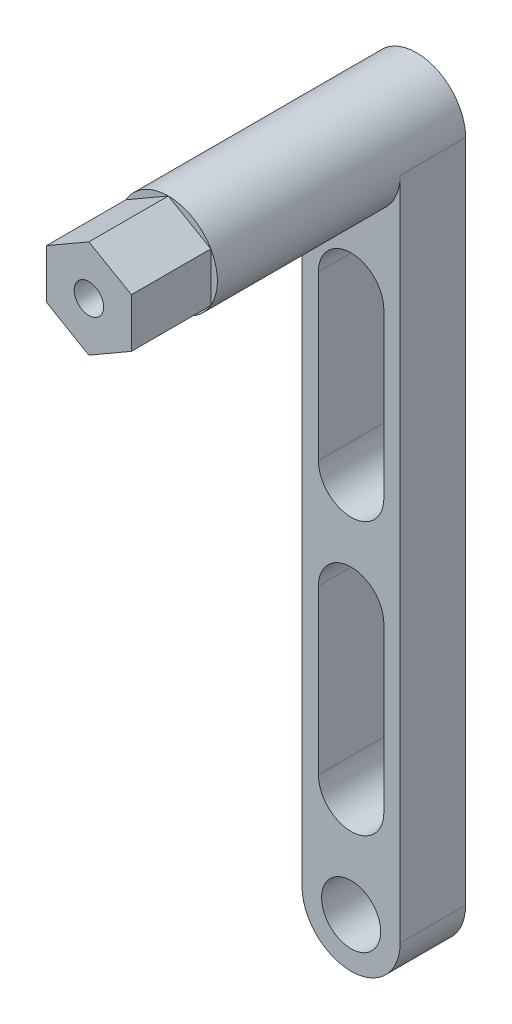
SolidWorks part; units mm, degrees
material "PEI"
ref_plane "Front Plane" through (0, 0, 0) normal (0, 0, 1) x (1, 0, 0)
ref_plane "Top Plane" through (0, 0, 0) normal (0, 1, 0) x (1, 0, 0)
ref_plane "Right Plane" through (0, 0, 0) normal (1, 0, 0) x (0, 0, -1)
sketch "Sketch1" plane through (0, 0, 0) normal (0, 0, 1) x (1, 0, 0)
  line L0 (0, -50.8) -> (0, 50.8) construction
  line L1 (-7.5, -50.8) -> (-7.5, 50.8)
  line L2 (7.5, -50.8) -> (7.5, 50.8)
  line L3 (0, -34.785) -> (0, -9.785) construction
  line L4 (-5, -34.785) -> (-5, -9.785)
  line L5 (5, -34.785) -> (5, -9.785)
  line L6 (0, 31.8) -> (0, 6.8) construction
  line L7 (5, 31.8) -> (5, 6.8)
  line L8 (-5, 31.8) -> (-5, 6.8)
  line L9 (-5, 19.3) -> (5, 19.3) construction
  line L10 (-5, -22.285) -> (5, -22.285) construction
  line L12 (0, 58.3) -> (0, 36.8) construction
  arc A0 (-7.5, -50.8) -> (7.5, -50.8) centre (0, -50.8) ccw
  arc A1 (7.5, 50.8) -> (-7.5, 50.8) centre (0, 50.8) ccw
  circle A2 centre (0, -50.8) radius 4.515
  arc A4 (-5, -34.785) -> (5, -34.785) centre (0, -34.785) ccw
  arc A5 (5, -9.785) -> (-5, -9.785) centre (0, -9.785) ccw
  arc A6 (5, 31.8) -> (-5, 31.8) centre (0, 31.8) ccw
  arc A7 (-5, 6.8) -> (5, 6.8) centre (0, 6.8) ccw
  circle A8 centre (0, 50.8) radius 7.5
  point P2 (0, 0)
  point P14 (0, -22.285)
  point P19 (0, 19.3)
  point P30 (0, -4.785)
  point P32 (0, -46.285)
  point P33 (0, -39.785)
  point P35 (0, 1.8)
  point P37 (0, 43.3)
  dimension "D3" = 9.03
  dimension "D1" = 101.6
  dimension "D2" = 15
  dimension "D4" = 10
  dimension "D5" = 6.5
  dimension "20" = 25
  dimension "D6" = 6.5
extrude "Boss-Extrude1" add sketch "Sketch1" along normal blind 10 contours A8 L1 A0 L2 A7 L8 A6 L7 A5 L5 A4 L4 A2 region at (-6.3987, 0, 0)
extrude "Boss-Extrude2" add sketch "Sketch1<4>" along normal blind 37.94 contours A1 A8 region at (0, 50.8, 0)
sketch "Sketch1<4>" plane through (0, 0, 0) normal (0, 0, 1) x (1, 0, 0) same geometry as "Sketch1"
sketch "Sketch2" plane through (0, 0, 37.94) normal (0, 0, 1) x (1, 0, 0)
  point P0 (0, 50.8)
sketch "Sketch3" plane through (0, 0, 37.94) normal (0, 0, 1) x (1, 0, 0)
  line L1 (0, 43.3) -> (6.4952, 47.05)
  line L2 (6.4952, 47.05) -> (6.4952, 54.55)
  line L3 (6.4952, 54.55) -> (0, 58.3)
  line L4 (0, 58.3) -> (-6.4952, 54.55)
  line L5 (-6.4952, 54.55) -> (-6.4952, 47.05)
  line L6 (-6.4952, 47.05) -> (0, 43.3)
  circle A0 centre (0, 50.8) radius 6.4952 construction
extrude "Boss-Extrude3" add sketch "Sketch3" along normal blind 12.14
sketch "Sketch4" plane through (0, 0, 50.08) normal (0, 0, 1) x (1, 0, 0)
  circle A0 centre (0, 50.8) radius 2.25
  dimension "D1" = 4.5
extrude "Cut-Extrude1" cut sketch "Sketch4" against normal blind 10 contours A0
